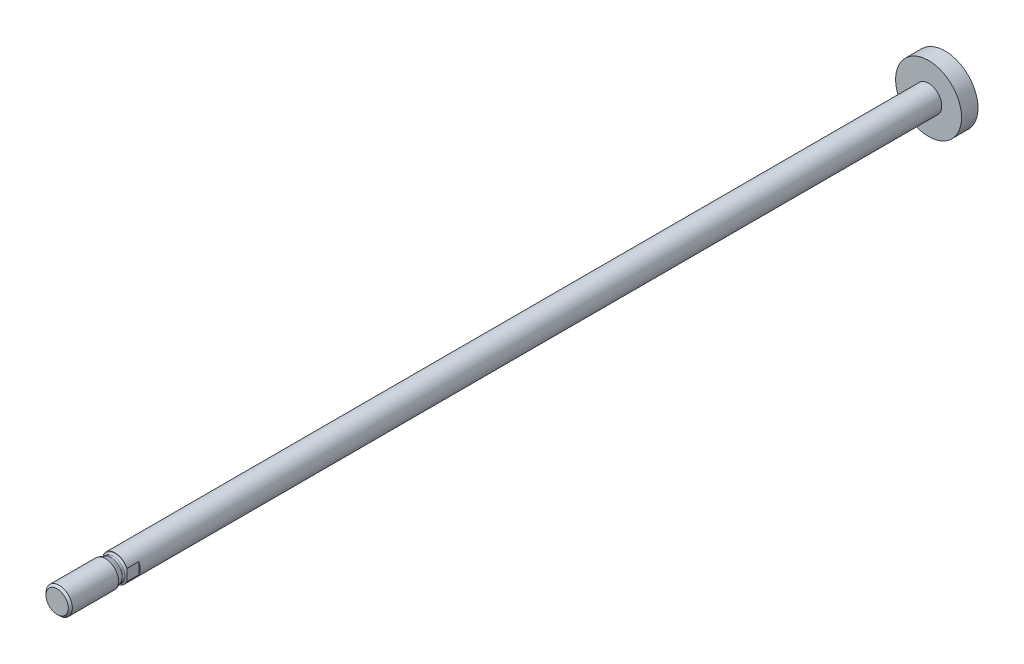
SolidWorks part; units mm, degrees
ref_plane "Ebene vorne" through (0, 0, 0) normal (0, 0, 1) x (1, 0, 0)
ref_plane "Ebene oben" through (0, 0, 0) normal (0, 1, 0) x (1, 0, 0)
ref_plane "Ebene rechts" through (0, 0, 0) normal (1, 0, 0) x (0, 0, -1)
sketch "Skizze1" plane through (0, 0, 0) normal (1, 0, 0) x (0, 0, -1)
  line L0 (-6, 0) -> (-6, 5)
  line L1 (-6, 5) -> (302.6, 5)
  line L2 (302.6, 5) -> (302.6, 12.5)
  line L3 (302.6, 12.5) -> (308.85, 12.5)
  line L4 (308.85, 12.5) -> (308.85, 0)
  line L5 (308.85, 0) -> (-6, 0)
  line L6 (308.85, 0) -> (-6, 0) construction
revolve "Rotation1" add sketch "Skizze1" angle 360 about L6 reverse direction yes
sketch "Skizze2" plane through (0, 0, 0) normal (1, 0, 0) x (0, 0, -1)
  line L0 (-28, 0) -> (-28, 4.233)
  line L1 (-28, 4.233) -> (-27.233, 5)
  line L2 (-27.233, 5) -> (-9.698, 5)
  line L3 (-9.698, 5) -> (-7.5994, 4.2362)
  line L4 (-7.3942, 4.2) -> (-6.6, 4.2)
  line L5 (-6, 4.8) -> (-6, 5)
  line L6 (-6, 5) -> (-5, 5)
  line L7 (-5, 5) -> (-5, 0)
  line L8 (-5, 0) -> (-28, 0)
  line L9 (-5, 0) -> (-28, 0) construction
  arc A0 (-7.5994, 4.2362) -> (-7.3942, 4.2) centre (-7.3942, 4.8) ccw
  arc A1 (-6.6, 4.2) -> (-6, 4.8) centre (-6.6, 4.8) ccw
revolve "Rotation2" add sketch "Skizze2" angle 360 about L9 reverse direction yes
cosmetic thread "Gewindedarstellung1" parameters "D1"=18.302, "D2"=8.466
ref_plane "Ebene1" through (0, 0, 6) normal (0, 0, 1) x (1, 0, 0)
ref_plane "Ebene2" through (0, 0, 1.5) normal (0, 0, 1) x (1, 0, 0)
sketch "Skizze3" plane through (0, 0, 1.5) normal (0, 0, 1) x (1, 0, 0)
  line L0 (-9, 18) -> (-9, -9)
  line L1 (-9, -9) -> (-4.5, -9)
  line L2 (-4.5, -9) -> (-4.5, 9)
  line L3 (-4.5, 9) -> (4.5, 9)
  line L4 (4.5, 9) -> (4.5, -9)
  line L5 (4.5, -9) -> (9, -9)
  line L6 (9, -9) -> (9, 18)
  line L7 (9, 18) -> (-9, 18)
extrude "Schnitt-Linear austragen1" cut sketch "Skizze3" along normal blind 5.5
ref_plane "Ebene3" through (0, 0, -619.5) normal (0, 0, 1) x (1, 0, 0)
ref_plane "Ebene4" through (0, 0, 17.667) normal (0, 0, 1) x (1, 0, 0)
ref_plane "Ebene5" through (0, 0, 15) normal (0, 0, 1) x (1, 0, 0)
ref_plane "FDT_KSAUFSATZ XY" through (0, 0, 15) normal (0, 0, 1) x (1, 0, 0)
ref_plane "FDT_KSAUFSATZ XZ" through (0, 0, 0) normal (0, 1, 0) x (1, 0, 0)
ref_plane "FDT_KSAUFSATZ YZ" through (0, 0, 0) normal (-1, 0, 0) x (0, 0, 1)
ref_axis "FDT_KSAUFSATZ X" through (80.9, 0, 15) along (-1, 0, 0)
ref_axis "FDT_KSAUFSATZ Y" through (0, 50, 15) along (0, -1, 0)
ref_axis "FDT_KSAUFSATZ Z" through (0, 0, 80.9) along (0, 0, -1)
sketch3d "FDT_KSAUFSATZ"
  point P0 (0, 0, 15)
ref_plane "FDT_NUT XY" through (0, 0, 15) normal (0, 0, 1) x (1, 0, 0)
ref_plane "FDT_NUT XZ" through (0, 0, 0) normal (0, 1, 0) x (1, 0, 0)
ref_plane "FDT_NUT YZ" through (0, 0, 0) normal (-1, 0, 0) x (0, 0, 1)
ref_axis "FDT_NUT X" through (80.9, 0, 15) along (-1, 0, 0)
ref_axis "FDT_NUT Y" through (0, 50, 15) along (0, -1, 0)
ref_axis "FDT_NUT Z" through (0, 0, 80.9) along (0, 0, -1)
sketch3d "FDT_NUT"
  point P0 (0, 0, 15)
ref_plane "KS XY" through (0, 0, 0) normal (0, 0, -1) x (-1, 0, 0)
ref_plane "KS XZ" through (0, 0, 0) normal (0, 1, 0) x (1, 0, 0)
ref_plane "KS YZ" through (0, 0, 0) normal (1, 0, 0) x (0, 0, -1)
ref_axis "KS X" through (-80.9, 0, 0) along (1, 0, 0)
ref_axis "KS Y" through (0, 50, 0) along (0, -1, 0)
ref_axis "KS Z" through (0, 0, -80.9) along (0, 0, 1)
sketch3d "KS"
  point P0 (0, 0, 0)
ref_plane "NUT1 XY" through (0, 0, 17.667) normal (0, 0, 1) x (1, 0, 0)
ref_plane "NUT1 XZ" through (0, 0, 0) normal (0, -1, 0) x (-1, 0, 0)
ref_plane "NUT1 YZ" through (0, 0, 0) normal (1, 0, 0) x (0, 0, -1)
ref_axis "NUT1 X" through (-80.9, 0, 17.667) along (1, 0, 0)
ref_axis "NUT1 Y" through (0, -50, 17.667) along (0, 1, 0)
ref_axis "NUT1 Z" through (0, 0, 80.9) along (0, 0, -1)
sketch3d "NUT1"
  point P0 (0, 0, 17.667)
